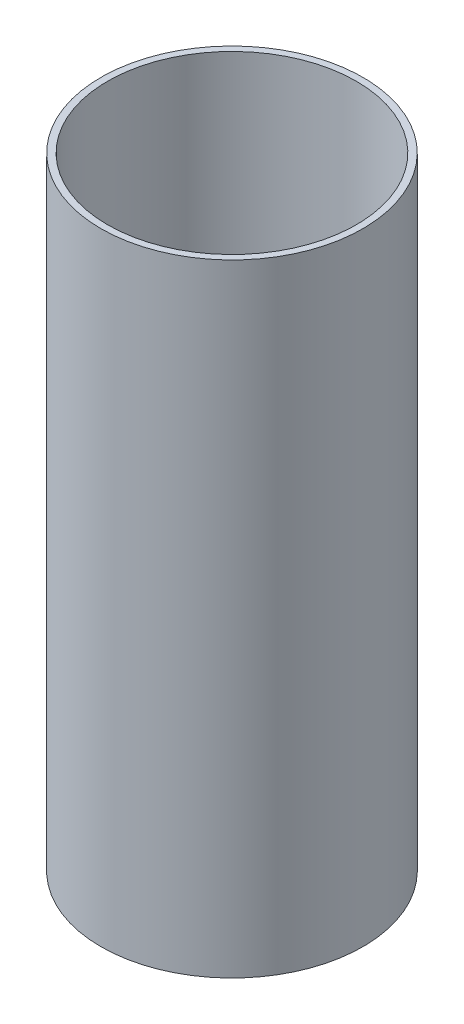
SolidWorks part; units mm, degrees
material "PVC Rigid"
ref_plane "Front Plane" through (0, 0, 0) normal (0, 0, 1) x (1, 0, 0)
ref_plane "Top Plane" through (0, 0, 0) normal (0, 1, 0) x (1, 0, 0)
ref_plane "Right Plane" through (0, 0, 0) normal (1, 0, 0) x (0, 0, -1)
sketch "Sketch1" plane through (0, 0, 0) normal (0, 1, 0) x (1, 0, 0)
  circle A0 centre (0, 0) radius 93.6625
  circle A1 centre (0, 0) radius 88.9
  dimension "D1" = 187.325
  dimension "D2" = 177.8
extrude "Boss-Extrude1" add sketch "Sketch1" along normal mid plane 444.5
ref_plane "Plane1" through (-93.6625, 0, 0) normal (-1, 0, 0) x (0, 0, 1)
sketch "Sketch3" plane through (-93.6625, 0, 0) normal (-1, 0, 0) x (0, 0, 1)
  line L0 (0, -103.0288) -> (0, 103.0288) construction
  line L1 (-88.9, -222.25) -> (88.9, -222.25) construction
  circle A0 centre (0, -215.9) radius 1.4351
  dimension "D1" = 2.8702
  dimension "D2" = 6.35
extrude "Cut-Extrude1" [suppressed] cut sketch "Sketch3" against normal blind 21.59
pattern_circular "CirPattern1" [suppressed] count 12 over 360 reverse direction yes of bodies 102
sketch "Sketch4" plane through (-93.6625, 0, 0) normal (-1, 0, 0) x (0, 0, 1)
  line L0 (0, -103.0288) -> (0, 103.0288) construction
  line L1 (93.6625, 222.25) -> (-93.6625, 222.25) construction
  circle A0 centre (0, 215.9) radius 1.4351
  dimension "D1" = 2.8702
  dimension "D2" = 6.35
extrude "Cut-Extrude2" [suppressed] cut sketch "Sketch4" against normal blind 34.798
pattern_circular "CirPattern2" [suppressed] count 3 over 360 reverse direction yes of bodies 104
sketch "Sketch9" [suppressed] plane through (-93.6625, 0, 0) normal (-1, 0, 0) x (0, 0, 1)
  line L0 (0, -103.0288) -> (0, 103.0288) construction
  circle A0 centre (0, 130.048) radius 1.4351
  circle A1 centre (0, 215.9) radius 1.4351 construction
  dimension "D1" = 85.852
  dimension "D2" = 2.8702
extrude "Cut-Extrude4" [suppressed] cut sketch "Sketch9" against normal blind 15.24
pattern_circular "CirPattern4" [suppressed] count 12 over 360 of bodies 108
sketch "Sketch7" [suppressed] plane through (-93.6625, 0, 0) normal (-1, 0, 0) x (0, 0, 1)
  line L0 (0, -103.0288) -> (0, 103.0288) construction
  circle A0 centre (0, 6.35) radius 1.4351
  circle A1 centre (0, -98.552) radius 1.4351
  circle A4 centre (0, 130.048) radius 1.4351 construction
  circle A5 centre (0, -215.9) radius 1.4351 construction
  dimension "D1" = 123.698
  dimension "D2" = 117.348
  dimension "D3" = 2.8702
  dimension "D4" = 2.8702
extrude "Cut-Extrude3" [suppressed] cut sketch "Sketch7" against normal blind 15.24
pattern_circular "CirPattern3" [suppressed] count 3 over 360 reverse direction yes of bodies 106
sketch "Sketch10" [suppressed] plane through (-93.6625, 0, 0) normal (-1, 0, 0) x (0, 0, 1)
  line L0 (0, -103.0288) -> (0, 103.0288) construction
  circle A0 centre (0, 205.74) radius 1.4351
  circle A1 centre (0, 215.9) radius 1.4351 construction
  dimension "D1" = 10.16
  dimension "D2" = 2.8702
extrude "Cut-Extrude5" [suppressed] cut sketch "Sketch10" against normal blind 21.082
pattern_circular "CirPattern5" [suppressed] count 12 over 360 of bodies 110
